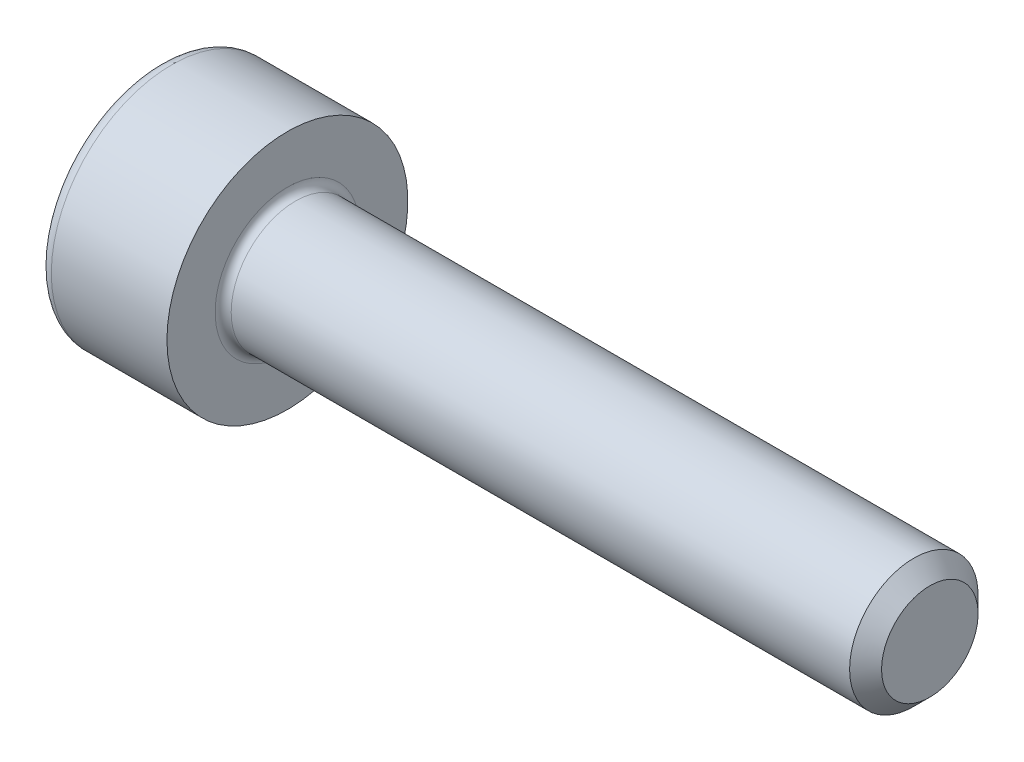
SolidWorks part; units mm, degrees
revolve "Base-Revolve" add sketch "BodySke"
sketch "BodySke" plane through (0, 0, 0) normal (0, 0, 1) x (1, 0, 0)
  line L0 (0, 0) -> (0, 1.5)
  line L1 (0, 1.5) -> (1.6, 1.5)
  line L2 (1.6, 1.5) -> (1.6, 0.8)
  line L3 (1.6, 0.8) -> (9.401, 0.8)
  line L4 (9.6, 0.601) -> (9.6, 0)
  line L5 (9.6, 0) -> (0, 0)
  line L6 (-31.75, 0) -> (127, 0) construction
  line L8 (9.6, 0.601) -> (9.401, 0.8)
  line L10 (9.6, -0.601) -> (9.401, -0.8) construction
  line L11 (1.95, 9.525) -> (1.95, 3.175) construction
  line L12 (1.6, 9.525) -> (1.6, 3.175) construction
  line L13 (-50.4, 9.525) -> (-50.4, 3.175) construction
  dimension "Diameter" = 1.6
  dimension "Head_dia" = 3
cosmetic thread "ThreadCosmetic" [suppressed]
fillet "Fillet1" radius 0.1 1 edges at (1.6, 0, 0.8)
fillet "Fillet2" radius 0.16 1 edges at (0, 0, 1.5)
ref_plane "Plane1" through (0, 0, 0) normal (0, 0, 1) x (1, 0, 0)
ref_plane "Plane2" through (0, 0, 0) normal (0, 1, 0) x (1, 0, 0)
ref_plane "Plane3" through (0, 0, 0) normal (1, 0, 0) x (0, 0, -1)
sketch "Sketch2" plane through (0, 0, 0) normal (0, 0, 1) x (1, 0, 0)
  line L0 (0, 0.76) -> (0.7, 0.76)
  line L1 (0.7, 0.76) -> (1.1388, 0)
  line L2 (-31.75, 0) -> (127, 0) construction
  line L3 (1.1388, 0) -> (0, 0)
  line L4 (0, 0) -> (0, 0.76)
  line L6 (0, 0) -> (47.625, 0) construction
  dimension "D1" = 0.76
  dimension "D2" = 60
revolve "Hex-PreBroach" cut sketch "Sketch2" angle 360 about L6
sketch "Sketch3" plane through (0, 0, 0) normal (-1, 0, 0) x (0, 0.5, 0.866)
  line L0 (0.4388, 0.76) -> (-0.4388, 0.76)
  line L1 (-0.4388, 0.76) -> (-0.8776, 0)
  line L2 (0.4388, 0.76) -> (0.8776, 0)
  line L3 (0.4388, -0.76) -> (0.8776, 0)
  line L4 (0.4388, -0.76) -> (-0.4388, -0.76)
  line L5 (-0.4388, -0.76) -> (-0.8776, 0)
  dimension "D1" = 0.76
  dimension "D2" = 0.76
extrude "Hex" cut sketch "Sketch3" against normal blind 0.7
sketch "ThdSchSke" plane through (0, 0, 0) normal (0, 0, 1) x (1, 0, 0)
  line L0 (2.65, -0.601) -> (2.5107, -0.8)
  line L1 (2.65, -0.601) -> (2.7893, -0.8)
  line L2 (2.7893, -0.8) -> (2.7893, -1)
  line L3 (-3.175, 0) -> (5.1513, 0) construction
  line L4 (0, 1.34) -> (0, -1.34) construction
  line L5 (2.7893, -1) -> (2.5107, -1)
  line L6 (2.5107, -1) -> (2.5107, -0.8)
  dimension "Diameter" = 1.6
  dimension "Thread_minor" = 1.202
  dimension "Start" = 2.65
revolve "ThreadSchematic" [suppressed] cut sketch "ThdSchSke" angle 360 about L3
pattern_linear "ThdSchPat" [suppressed]
equation "\"D2@Sketch3\" = \"Hex_size@Sketch3\" / 2"
equation "\"D1@Sketch3\" = \"Hex_size@Sketch3\" / 2"
equation "\"D1@Sketch2\" = \"Hex_size@Sketch3\" / 2"
equation "\"Thread_minor@ThreadCosmetic\"  =  \"Minor_dia@BodySke\""
equation "\"Depth@Sketch2\" =  \"Key_eng@Hex\""
equation "\"Thread_length@ThreadCosmetic\" = ((sgn( (\"Length@BodySke\" - \"Advance@BodySke\" * 3.0) - \"Thread_nom@BodySke\" )-1)*( (\"Length@BodySke\" - \"Advance@BodySke\" * 3.0) - \"Thread_nom@BodySke\" ))/-2+ \"Thread_nom@BodySke\""
equation "\"Thread_minor@ThdSchSke\" = \"Minor_dia@BodySke\""
equation "\"Diameter@ThdSchSke\" = \"Diameter@BodySke\""
equation "\"Overcut@ThdSchSke\" = \"Diameter@BodySke\" * 1.25"
equation "\"Start@ThdSchSke\" = \"Head_ht@BodySke\" + \"Length@BodySke\" - \"Thread_length@ThreadCosmetic\"  '---Non-countersunk---"
equation "\"Num_threads@ThdSchPat\" = int( \"Thread_length@ThreadCosmetic\" / \"Advance@BodySke\" + 0.999 )  + 1"
equation "\"Advance@ThdSchPat\" = \"Thread_length@ThreadCosmetic\" /  (\"Num_threads@ThdSchPat\" - 1) 'relax it"
equation "\"Num_threads@ThdSchPat\" = \"Num_threads@ThdSchPat\" - sgn( \"Num_threads@ThdSchPat\" - 1) '---chamfered tips only---"
